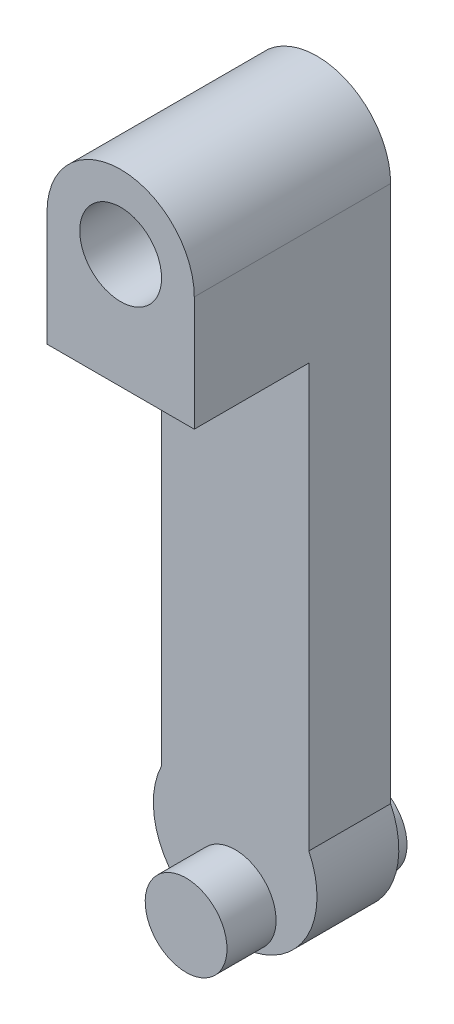
SolidWorks part; units mm, degrees
ref_plane "Front Plane" through (0, 0, 0) normal (0, 0, 1) x (1, 0, 0)
ref_plane "Top Plane" through (0, 0, 0) normal (0, 1, 0) x (1, 0, 0)
ref_plane "Right Plane" through (0, 0, 0) normal (1, 0, 0) x (0, 0, -1)
sketch "Sketch1" plane through (0, 0, 0) normal (0, 0, 1) x (1, 0, 0)
  line L0 (-5.715, 0) -> (-5.715, -41.6821)
  line L1 (5.715, 0) -> (5.715, -41.6821)
  line L2 (-5.715, -44.45) -> (5.715, -44.45) construction
  line L3 (-5.715, -41.6821) -> (-5.715, -44.45) construction
  line L4 (5.715, -41.6821) -> (5.715, -44.45) construction
  circle A0 centre (0, 0) radius 3.175
  arc A1 (5.715, 0) -> (-5.715, 0) centre (0, 0) ccw
  arc A2 (-5.715, -41.6821) -> (5.715, -41.6821) centre (0, -44.45) ccw
  arc A3 (5.715, -41.6821) -> (-5.715, -41.6821) centre (0, -44.45) ccw construction
  dimension "D1" = 6.35
  dimension "D4" = 12.7
  dimension "D2" = 11.43
  dimension "D3" = 44.45
extrude "Boss-Extrude1" add sketch "Sketch1" along normal blind 6.35
sketch "Sketch2" plane through (0, 0, 6.35) normal (0, 0, 1) x (1, 0, 0)
  circle A0 centre (0, -47.625) radius 3.175
  point P0 (0, 0)
  point P5 (0, 0)
  dimension "D1" = 6.35
  dimension "1.85" = 47.625
extrude "Boss-Extrude2" add sketch "Sketch2" along normal blind 3.81
extrude "Boss-Extrude3" add sketch "Sketch2<2>" against normal blind 3.81 from surface starting at face at (0, -21.6918, 0)
sketch "Sketch2<2>" plane through (0, 0, 6.35) normal (0, 0, 1) x (1, 0, 0) same geometry as "Sketch2"
sketch "Sketch4" plane through (0, 0, 6.35) normal (0, 0, 1) x (1, 0, 0)
  line L108 (-5.715, -8.89) -> (5.715, -8.89)
  line L110 (-5.715, 0) -> (-5.715, -41.6821)
  line L111 (5.715, -41.6821) -> (5.715, 0)
  line L112 (-5.715, 0) -> (-5.715, -8.89)
  line L113 (5.715, -8.89) -> (5.715, 0)
  circle A213 centre (0, 0) radius 3.175
  arc A214 (5.715, 0) -> (-5.715, 0) centre (0, 0) ccw
  arc A215 (5.715, 0) -> (-5.715, 0) centre (0, 0) ccw
  dimension "D3" = 6.35
  dimension "D2" = 8.89
  dimension "D1" = 0
extrude "Boss-Extrude4" add sketch "Sketch4" along normal blind 8.89
